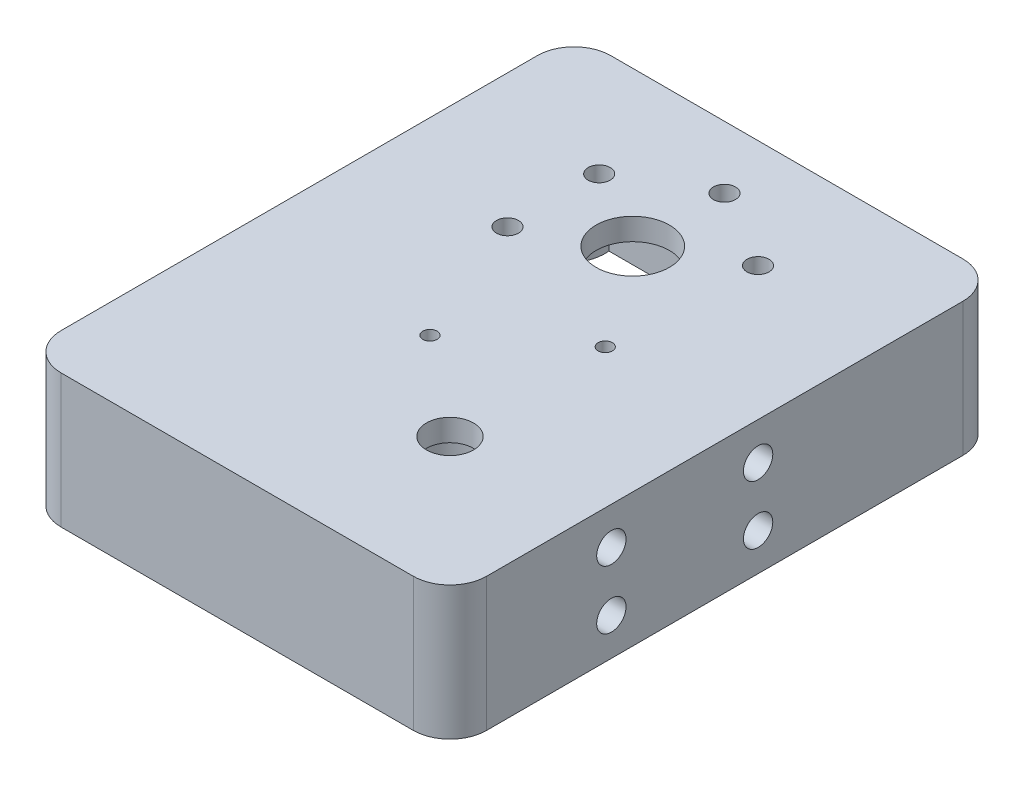
SolidWorks part; units mm, degrees
ref_plane "Front Plane" through (0, 0, 0) normal (0, 0, 1) x (1, 0, 0)
ref_plane "Top Plane" through (0, 0, 0) normal (0, 1, 0) x (1, 0, 0)
ref_plane "Right Plane" through (0, 0, 0) normal (1, 0, 0) x (0, 0, -1)
sketch "Sketch1" plane through (0, 0, 0) normal (0, 1, 0) x (1, 0, 0)
  line L0 (0, 0) -> (10, -13.7477) construction
  line L1 (10, -13.7477) -> (-3.3043, -24.3305) construction
  line L2 (-3.3043, -24.3305) -> (10, -34.9132) construction
  line L9 (-29, 21) -> (-29, -53.9132)
  line L10 (-29, -53.9132) -> (29, -53.9132)
  line L11 (29, -53.9132) -> (29, 21)
  line L12 (29, 21) -> (-29, 21)
  circle A2 centre (0, 0) radius 6.5 construction
  circle A4 centre (-3.3043, -24.3305) radius 12 construction
  circle A5 centre (10, -13.7477) radius 12 construction
  circle A13 centre (0, 0) radius 5
  circle A18 centre (0, 0) radius 18 construction
  circle A29 centre (10, -34.9132) radius 12 construction
  circle A30 centre (10, -13.7477) radius 0.975
  circle A31 centre (-3.3043, -24.3305) radius 0.975
  circle A32 centre (10, -34.9132) radius 3.2
  circle A33 centre (10, -34.9132) radius 8 construction
  point P13 (22, -34.9132)
  point P15 (-3.3043, -36.3305)
  point P20 (0, 0)
  point P38 (0, 21)
  point P39 (0, 18)
  point P48 (10, -46.9132)
  dimension "D2" = 6.4
  dimension "D3" = 13
  dimension "D4" = 17
  dimension "D5" = 77
  dimension "D6" = 24
  dimension "D9" = 58
  dimension "D10" = 3
  dimension "D11" = 36
  dimension "D12" = 7
  dimension "D7" = 19
  dimension "1" = 10
  dimension "D1" = 1.95
  dimension "D8" = 16
extrude "Boss-Extrude1" add sketch "Sketch1" along normal blind 3 contours L11 L12 L9 L10 A32 A31 A30 A13 region at (-0.0808, 0, 16.6182)
sketch "Sketch6" plane through (0, 0, 0) normal (0, 1, 0) x (1, 0, 0)
  line L0 (-29, 21) -> (29, -53.9132) construction
  line L1 (-29, -53.9132) -> (29, 21) construction
  line L2 (29, -53.9132) -> (29, 21) construction
  line L3 (-19.2407, -48.9132) -> (19.2407, -48.9132)
  line L4 (-24, -42.9249) -> (-24, 10.0117)
  line L5 (-19.2407, 16) -> (19.2407, 16)
  line L6 (24, -42.9249) -> (24, 10.0117)
  line L7 (-17.4226, -38.9598) -> (24.7147, 15.465) construction
  line L8 (-15.7648, 14.3966) -> (15.2178, -46.2393) construction
  line L9 (0, -16.4566) -> (55.9921, -16.4566) construction
  line L10 (-29, -53.9132) -> (29, -53.9132)
  line L11 (-29, -53.9132) -> (-29, 21)
  line L12 (-29, 21) -> (29, 21)
  line L13 (29, -53.9132) -> (29, 21)
  line L14 (-29, -53.9132) -> (29, 21) construction
  line L15 (-29, 21) -> (29, -53.9132) construction
  line L16 (0, -16.4566) -> (0, 26.1978) construction
  circle A0 centre (24.7147, 15.465) radius 1.5
  arc A1 (19.2407, 16) -> (24, 10.0117) centre (24.7147, 15.465) ccw
  circle A2 centre (24.7147, -48.3783) radius 1.5
  arc A3 (19.2407, -48.9132) -> (24, -42.9249) centre (24.7147, -48.3783) cw
  arc A4 (-19.2407, 16) -> (-24, 10.0117) centre (-24.7147, 15.465) cw
  circle A5 centre (-24.7147, 15.465) radius 1.5
  circle A6 centre (-24.7147, -48.3783) radius 1.5
  arc A7 (-19.2407, -48.9132) -> (-24, -42.9249) centre (-24.7147, -48.3783) ccw
  point P8 (0, -16.4566)
  point P15 (0, -16.4566)
  dimension "D2" = 3
  dimension "D3" = 4
  dimension "D1" = 5
  dimension "D4" = 7
  dimension "5" = 5
extrude "Boss-Extrude5" add sketch "Sketch6" against normal blind 15.2
sketch "Sketch7" plane through (0, 0, 0) normal (0, -1, 0) x (1, 0, 0)
  circle A0 centre (10, 34.9132) radius 5
  circle A1 centre (10, 34.9132) radius 8
  dimension "D1" = 10
  dimension "D2" = 3
extrude "Boss-Extrude6" add sketch "Sketch7" along normal blind 4
sketch "Sketch2" plane through (0, 0, 0) normal (0, 1, 0) x (1, 0, 0)
  line L0 (0, 0) -> (50.7044, 0) construction
  line L1 (0, 0) -> (10.8253, -6.25) construction
  circle A0 centre (0, 0) radius 12.5 construction
  circle A7 centre (10.8253, -6.25) radius 1.5 construction
  circle A8 centre (0, -12.5) radius 1.5 construction
  circle A9 centre (-10.8253, -6.25) radius 1.5
  circle A10 centre (-10.8253, 6.25) radius 1.5
  circle A11 centre (0, 12.5) radius 1.5
  circle A12 centre (10.8253, 6.25) radius 1.5
  point P17 (0, 0)
  dimension "D1" = 25
  dimension "D2" = 30
  dimension "D3" = 3
  dimension "D4" = 6
extrude "Cut-Extrude7" cut sketch "Sketch2" along normal blind 7
sketch "Sketch5" plane through (29, 0, 0) normal (1, 0, 0) x (0, 0, -1)
  line L0 (21, 3) -> (21, -15.2) construction
  line L1 (-34.9132, -4) -> (-34.9132, 0) construction
  line L2 (-31.9132, -6.1) -> (-11.9132, -6.1) construction
  line L3 (-31.9132, -10.1) -> (-31.9132, -2.1) construction
  line L4 (-11.9132, -10.1) -> (-11.9132, -2.1) construction
  circle A0 centre (-31.9132, -2.1) radius 2
  circle A1 centre (-31.9132, -10.1) radius 2
  circle A2 centre (-11.9132, -10.1) radius 2
  circle A3 centre (-11.9132, -2.1) radius 2
  point P0 (21, -6.1)
  point P1 (-21.9132, -6.1)
  point P4 (-21.9132, -6.1)
  point P11 (-31.9132, -6.1)
  point P19 (-11.9132, -6.1)
  dimension "D2" = 4
  dimension "D1" = 20
  dimension "D3" = 8
  dimension "D4" = 3
extrude "Cut-Extrude8" cut sketch "Sketch5" against normal blind 7
ref_plane "Plane1" through (0, 0, 0) normal (1, 0, 0) x (0, 0, -1)
mirror "Mirror1" about plane through (0, 0, 0) normal (1, 0, 0) of "Cut-Extrude8"
fillet "Fillet1" radius 5 4 edges at (29, -6.1, -21) (29, -6.1, 53.9132) (-29, -6.1, 53.9132) (-29, -6.1, -21)
sketch "Sketch8" plane through (0, 0, 0) normal (0, 1, 0) x (1, 0, 0)
  circle A0 centre (-3.3043, -24.3305) radius 0.975
  circle A1 centre (-3.3043, -24.3305) radius 4
  circle A2 centre (-3.3043, -24.3305) radius 0.975 construction
  dimension "D1" = 8
extrude "Boss-Extrude7" add sketch "Sketch8" against normal blind 5.01
